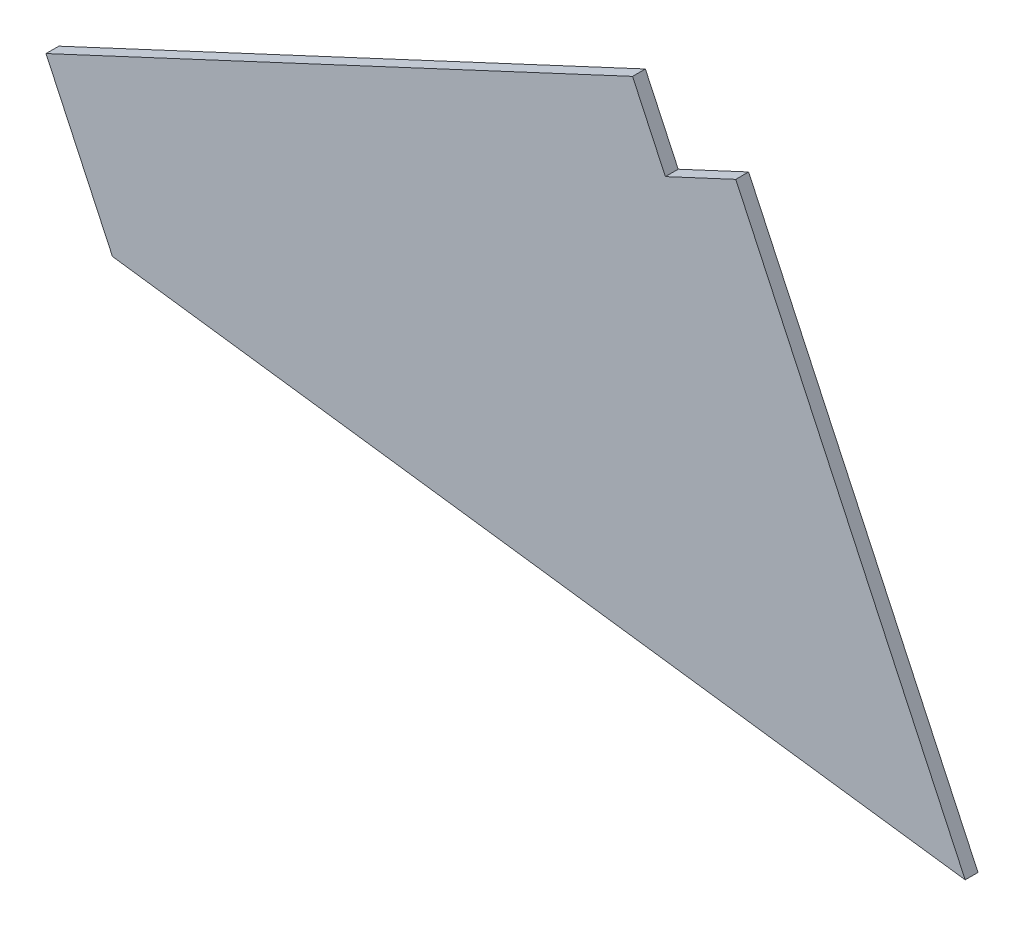
SolidWorks part; units mm, degrees
material "Balsa"
ref_plane "Front Plane" through (0, 0, 0) normal (0, 0, 1) x (1, 0, 0)
ref_plane "Top Plane" through (0, 0, 0) normal (0, 1, 0) x (1, 0, 0)
ref_plane "Right Plane" through (0, 0, 0) normal (1, 0, 0) x (0, 0, -1)
sketch "Sketch1" plane through (0, 0, 0) normal (0, 0, 1) x (1, 0, 0)
  line L0 (344.8461, -37.3321) -> (125.2807, -8.1077)
  line L1 (125.2807, -8.1077) -> (108.169, 28.5884)
  line L2 (108.169, 28.5884) -> (259.1989, 99.0148)
  line L3 (-63.4467, -51.4373) -> (255.5737, 97.3243) construction
  line L4 (259.1989, 99.0148) -> (267.6513, 80.8887)
  line L5 (267.6513, 80.8887) -> (285.7774, 89.341)
  line L6 (285.7774, 89.341) -> (344.8461, -37.3321)
  line L7 (327.4362, 0.0035) -> (398.701, -152.8244) construction
  line L8 (125.2807, -8.1077) -> (344.8461, -37.3321) construction
  line L9 (108.169, 28.5884) -> (125.2807, -8.1077) construction
  dimension "D1" = 20
  dimension "D2" = 20
extrude "Boss-Extrude1" add sketch "Sketch1" against normal blind 3.3
